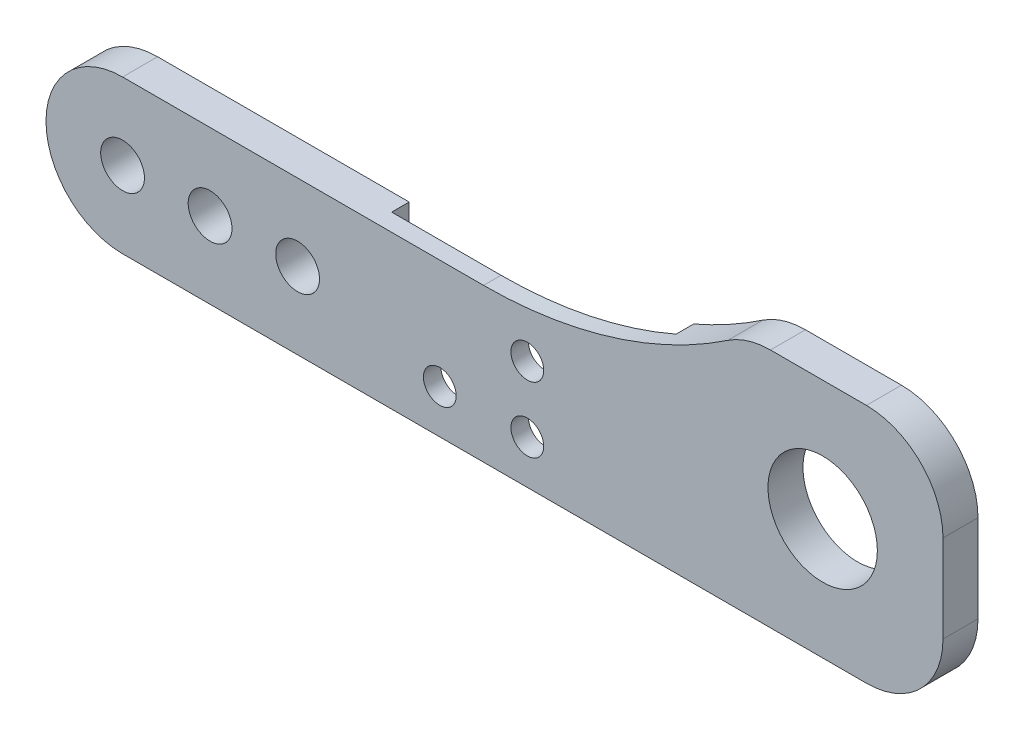
SolidWorks part; units mm, degrees
ref_plane "Front Plane" through (0, 0, 0) normal (0, 0, 1) x (1, 0, 0)
ref_plane "Top Plane" through (0, 0, 0) normal (0, 1, 0) x (1, 0, 0)
ref_plane "Right Plane" through (0, 0, 0) normal (1, 0, 0) x (0, 0, -1)
sketch "Sketch1" plane through (0, 0, 0) normal (0, 0, 1) x (1, 0, 0)
  line L0 (0, 7) -> (33, 7)
  line L1 (68, -7) -> (0, -7)
  line L5 (59.2298, 15) -> (68, 15)
  line L6 (75, 0) -> (75, 8)
  arc A1 (0, -7) -> (0, 7) centre (0, 0) cw
  arc A2 (33, 7) -> (55.3232, 13.8085) centre (33, 47) ccw
  arc A3 (68, -7) -> (75, 0) centre (68, 0) ccw
  arc A4 (68, 15) -> (75, 8) centre (68, 8) cw
  arc A5 (59.2298, 15) -> (55.3232, 13.8085) centre (59.2298, 8) ccw
  point P3 (75, -7)
  point P15 (75, 15)
  point P18 (57, 15)
  dimension "D2" = 7
  dimension "D4" = 40
  dimension "D1" = 7
  dimension "D3" = 22
  dimension "D5" = 18
  dimension "D6" = 75
extrude "Boss-Extrude1" add sketch "Sketch1" along normal blind 3.2
sketch "Sketch2" plane through (0, 0, 3.2) normal (0, 0, 1) x (1, 0, 0)
  line L0 (-7, 0) -> (-7, -7) construction
  line L6 (0, 0) -> (8, 0) construction
  line L7 (8, 0) -> (16, 0) construction
  line L8 (-7, -7) -> (0, -7) construction
  circle A0 centre (0, 0) radius 2
  circle A2 centre (8, 0) radius 2
  circle A5 centre (16, 0) radius 2
  arc A6 (0, 7) -> (0, -7) centre (0, 0) ccw construction
  dimension "D1" = 4
  dimension "D2" = 8
extrude "Cut-Extrude1" cut sketch "Sketch2" against normal up to surface (3.2 mm away) up to face at (47.7635, 5.6039, 0)
sketch "Sketch3" plane through (0, 0, 3.2) normal (0, 0, 1) x (1, 0, 0)
  line L0 (75, 0) -> (75, 8) construction
  line L2 (64, 4) -> (75, 4) construction
  line L3 (64, 4) -> (64, -7) construction
  line L4 (0, -7) -> (68, -7) construction
  circle A0 centre (64, 4) radius 5
  dimension "D1" = 10
extrude "Cut-Extrude2" cut sketch "Sketch3" against normal up to surface (3.2 mm away) up to face at (2, 0, 0)
sketch "Sketch4" plane through (0, 0, 0) normal (0, 0, -1) x (-1, 0, 0)
  line L0 (0, -7) -> (-68, -7) construction
  line L1 (-49, -7) -> (-23, -7)
  line L2 (-49, -7) -> (-49, 10.3394)
  line L3 (-49, 10.3394) -> (-23, 10.3394)
  line L4 (-23, -7) -> (-23, 10.3394)
  line L5 (-75, 0) -> (-75, 8) construction
  arc A0 (-55.3232, 13.8085) -> (-33, 7) centre (-33, 47) ccw construction
  dimension "D1" = 26
  dimension "D2" = 26
extrude "Cut-Extrude3" cut sketch "Sketch4" against normal blind 1.6
hole_wizard "Ø3.0mm Dowel Hole2" positions "Sketch9" profile "Sketch10" hole size "Ø3.0" standard "ANSI Metric" end condition through all
sketch "Sketch9" plane through (0, 0, 1.6) normal (0, 0, -1) x (-1, 0, 0)
  line L0 (-23, -7) -> (-23, 7) construction
  line L1 (-49, -7) -> (-23, -7) construction
  point P0 (-37, 3)
  point P3 (-37, -3)
  point P6 (-29, -3)
  point P9 (0, 0)
  point P10 (0, 0)
  point P11 (0, 0)
  dimension "D1" = 8
  dimension "D2" = 6
  dimension "D3" = 6
  dimension "D4" = 4
sketch "Sketch10" plane through (37, 3, 1.6) normal (1, 0, 0) x (0, 1, 0)
  line L0 (0, 0) -> (0, 1.6)
  line L1 (0, 1.6) -> (1.5, 1.6)
  line L2 (1.5, 1.6) -> (1.5, 0)
  line L5 (1.5, 0) -> (0, 0)
  line L11 (0, -6.35) -> (0, 107.95) construction
  dimension "Thru Hole Dia." = 3
  dimension "Thru Hole Depth" = 1.6
